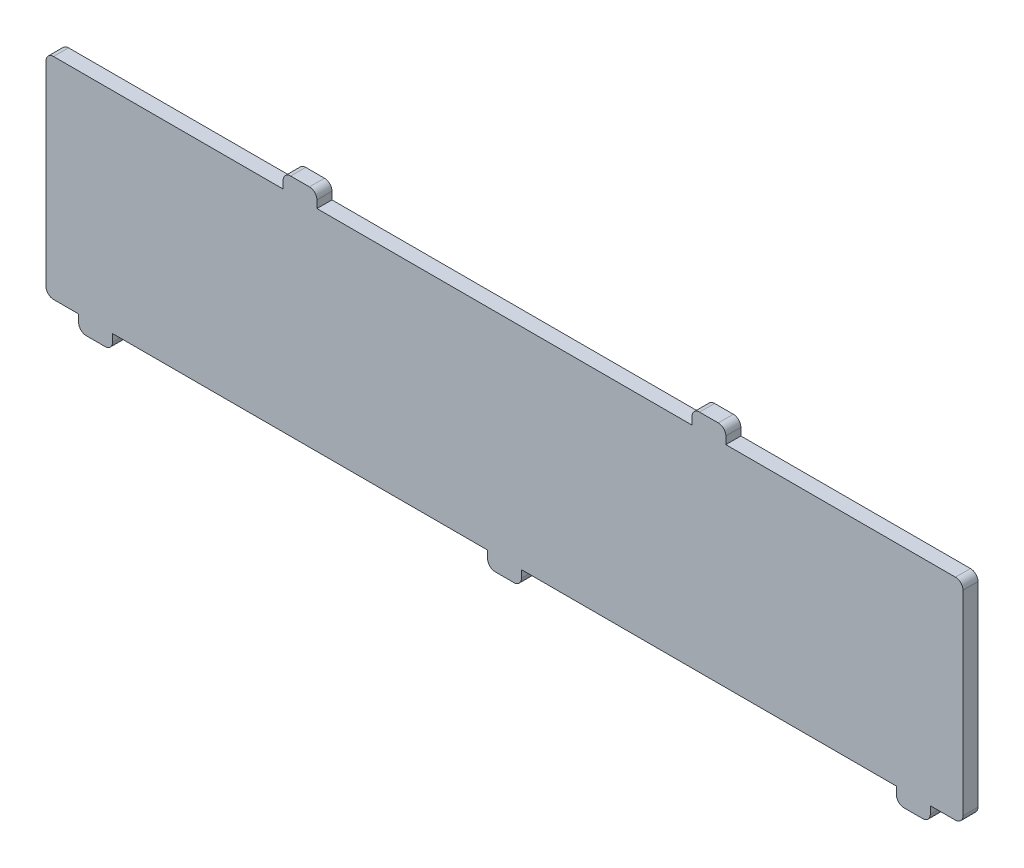
SolidWorks part; units mm, degrees
ref_plane "前基準面" through (0, 0, 0) normal (0, 0, 1) x (1, 0, 0)
ref_plane "上基準面" through (0, 0, 0) normal (0, 1, 0) x (1, 0, 0)
ref_plane "右基準面" through (0, 0, 0) normal (1, 0, 0) x (0, 0, -1)
sketch "Sketch1" plane through (0, 0, 0) normal (0, 0, 1) x (1, 0, 0)
  line L0 (0, 0) -> (0, -31.2064) construction
  line L1 (-61, 14) -> (61, 14)
  line L2 (-61, 14) -> (-61, -14)
  line L3 (-61, -14) -> (61, -14)
  line L4 (61, 14) -> (61, -14)
  line L5 (-61, 14) -> (61, -14) construction
  line L6 (-61, -14) -> (61, 14) construction
  line L7 (0, -31.2064) -> (0, 29.4941) construction
  line L8 (-2.25, -14) -> (2.25, -16) construction
  line L9 (-2.25, -14) -> (2.25, -14)
  line L10 (-2.25, -14) -> (-2.25, -16)
  line L11 (-2.25, -16) -> (2.25, -16)
  line L12 (2.25, -14) -> (2.25, -16)
  line L13 (-2.25, -16) -> (2.25, -14) construction
  line L14 (-56.65, -14) -> (-52.15, -16) construction
  line L15 (-56.65, -14) -> (-52.15, -14)
  line L16 (-56.65, -14) -> (-56.65, -16)
  line L17 (-56.65, -16) -> (-52.15, -16)
  line L18 (-52.15, -14) -> (-52.15, -16)
  line L19 (-52.15, -14) -> (-56.65, -16) construction
  line L20 (56.65, -16) -> (52.15, -16)
  line L21 (52.15, -14) -> (52.15, -16)
  line L22 (56.65, -14) -> (52.15, -14)
  line L23 (56.65, -14) -> (56.65, -16)
  line L24 (-54.4, -15) -> (-54.4, 18.4346) construction
  line L25 (0, -15.6032) -> (0, 17.9346) construction
  line L26 (52.15, -14) -> (56.65, -16) construction
  line L27 (56.65, -14) -> (52.15, -16) construction
  line L28 (-29.45, 16) -> (-24.95, 14) construction
  line L29 (-29.45, 14) -> (-24.95, 14)
  line L30 (-29.45, 14) -> (-29.45, 16)
  line L31 (-29.45, 16) -> (-24.95, 16)
  line L32 (-24.95, 14) -> (-24.95, 16)
  line L33 (-24.95, 16) -> (-29.45, 14) construction
  line L34 (29.45, 16) -> (24.95, 16)
  line L35 (24.95, 14) -> (24.95, 16)
  line L36 (29.45, 14) -> (24.95, 14)
  line L37 (29.45, 14) -> (29.45, 16)
  point P0 (0, 0)
  point P13 (0, -15)
  point P18 (-54.4, -15)
  point P19 (0, -15.6032)
  point P32 (-27.2, 15)
  dimension "D1" = 28
  dimension "D2" = 122
  dimension "D3" = 2
  dimension "D4" = 4.5
  dimension "D5" = 2
  dimension "D6" = 4.5
  dimension "D7" = 54.4
  dimension "D8" = 2
  dimension "D9" = 4.5
  dimension "D10" = 27.2
extrude "Boss-Extrude1" add sketch "Sketch1" along normal mid plane 2 contours L4 L1 L2 L3 | L12 L3 L10 L11 | L1 L37 L34 L35 | L1 L32 L31 L30 | L18 L17 L16 L15 | L23 L20 L21 L22 region at (0, 0, 0) region at (-27.2, 15, 0) region at (27.2, 15, 0) region at (0, -15, 0)
fillet "Fillet1" radius 1 14 edges at (-61, 14, 0) (-61, -14, 0) (-52.15, -16, 0) (-56.65, -16, 0) (2.25, -16, 0) (-2.25, -16, 0) (52.15, -16, 0) (56.65, -16, 0) (61, -14, 0) (61, 14, 0) (29.45, 16, 0) (24.95, 16, 0) (-24.95, 16, 0) (-29.45, 16, 0)
